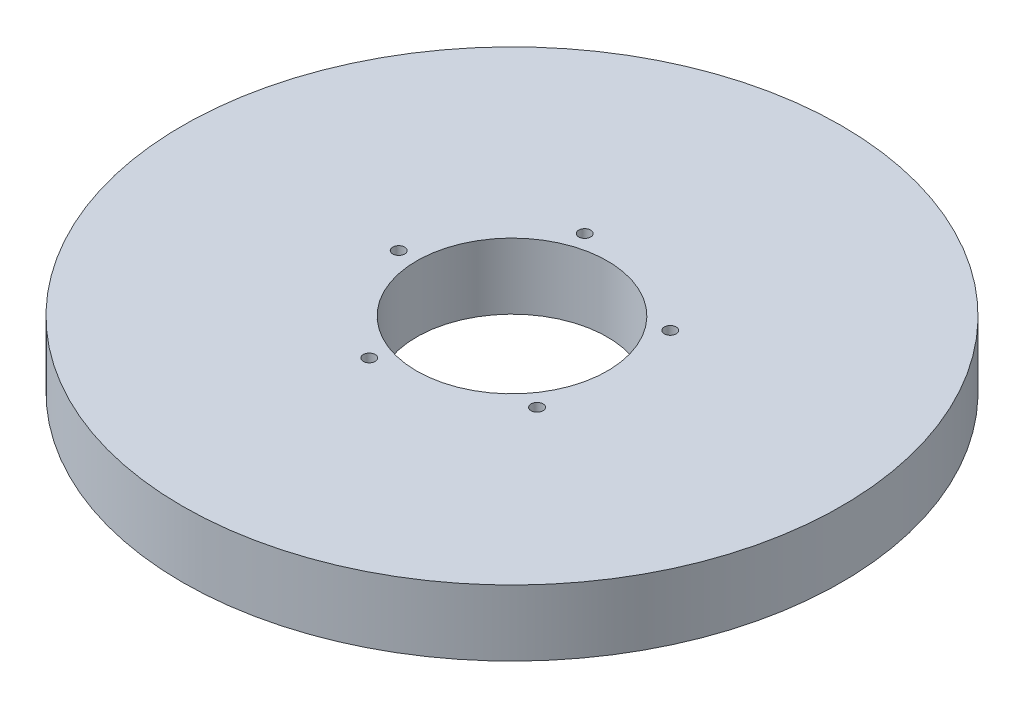
SolidWorks part; units mm, degrees
ref_plane "Front Plane" through (0, 0, 0) normal (0, 0, 1) x (1, 0, 0)
ref_plane "Top Plane" through (0, 0, 0) normal (0, 1, 0) x (1, 0, 0)
ref_plane "Right Plane" through (0, 0, 0) normal (1, 0, 0) x (0, 0, -1)
sketch "Sketch1" plane through (0, 0, 0) normal (0, 1, 0) x (1, 0, 0)
  circle A0 centre (0, 0) radius 95
  dimension "FLANGE_OD" = 190
extrude "Boss-Extrude1" add sketch "Sketch1" along normal blind 19
sketch "Sketch2" plane through (0, 0, 0) normal (0, 1, 0) x (1, 0, 0)
  circle A0 centre (0, 0) radius 27.5
  dimension "BORE_D" = 55
extrude "Cut-Extrude1" cut sketch "Sketch2" along normal through all
sketch "Sketch3" plane through (0, 19, 0) normal (0, 1, 0) x (1, 0, 0)
  circle A0 centre (0, 0) radius 32.6556 construction
  circle A1 centre (-32.6556, 0) radius 1.7305
  dimension "BOLT_D" = 3.4609
  dimension "BOLT_PCD" = 65.3112
extrude "Cut-Extrude2" cut sketch "Sketch3" against normal blind 14.2447
pattern_circular "CirPattern1" count 5 over 360 about axis through (0, 0, 0) along (0, 1, 0) of "Cut-Extrude2"
